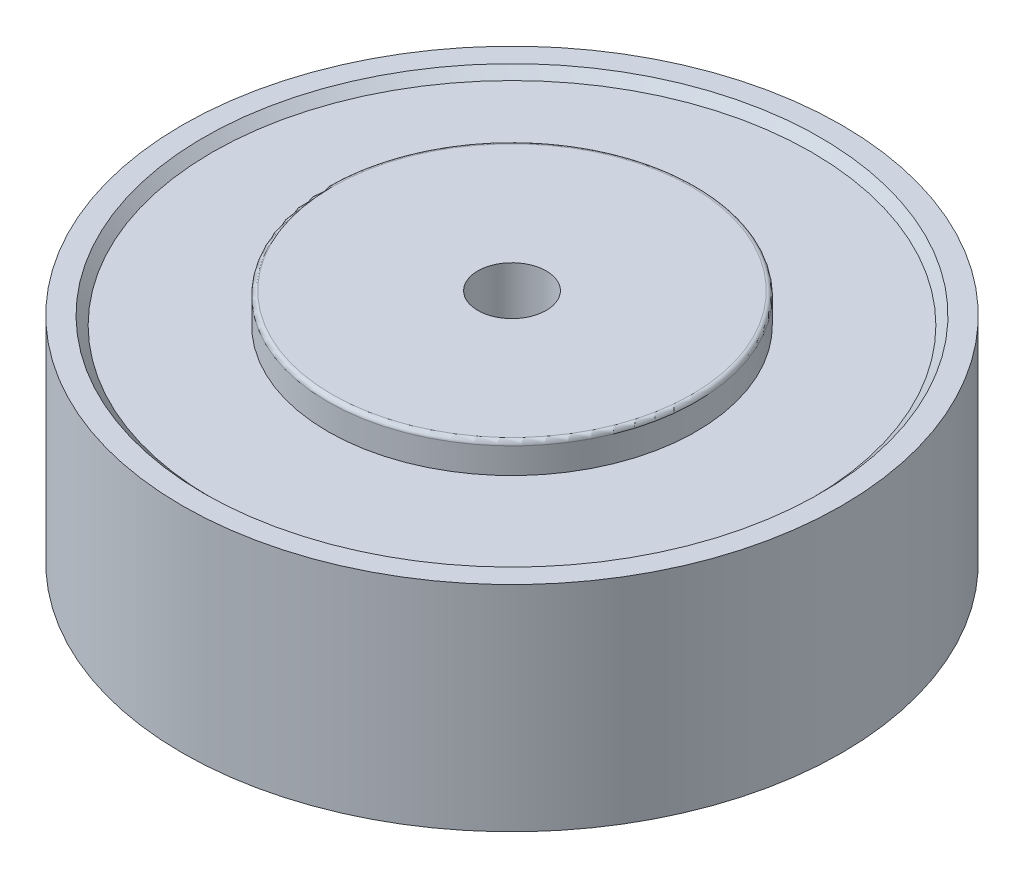
SolidWorks part; units mm, degrees
material "AISI 321 軟ｽﾃﾝﾚｽ鋼 (SS)"
ref_plane "正面" through (0, 0, 0) normal (0, 0, 1) x (1, 0, 0)
ref_plane "平面" through (0, 0, 0) normal (0, 1, 0) x (1, 0, 0)
ref_plane "右側面" through (0, 0, 0) normal (1, 0, 0) x (0, 0, -1)
sketch "ｽｹｯﾁ1" plane through (0, 0, 0) normal (0, 1, 0) x (1, 0, 0)
  arc A0 (2.7221, 38.4036) -> (35.9809, 13.6975) centre (0, 0) ccw
  arc A1 (1.3963, 35.9729) -> (34.0367, 11.7261) centre (0, 0) ccw
  circle A2 centre (0, 0) radius 38.5
extrude "ﾎﾞｽ - 押し出し1" add sketch "ｽｹｯﾁ1" along normal blind 25 contours A0 A2 region at (0, 0, 0)
sketch "ｽｹｯﾁ2" plane through (0, 25, 0) normal (0, 1, 0) x (1, 0, 0)
  arc A0 (1.3963, 35.9729) -> (34.0367, 11.7261) centre (0, 0) ccw
  circle A1 centre (0, 0) radius 36
extrude "ｶｯﾄ - 押し出し3" cut sketch "ｽｹｯﾁ2" against normal blind 1 contours A0 A1 region at (0, 25, 0)
sketch "ｽｹｯﾁ3" plane through (0, 0, 0) normal (0, -1, 0) x (1, 0, 0)
  arc A0 (1.3963, 35.9729) -> (34.0367, 11.7261) centre (0, 0) ccw
  circle A1 centre (0, 0) radius 36
extrude "ｶｯﾄ - 押し出し4" cut sketch "ｽｹｯﾁ3" against normal blind 1 contours A0 A1 region at (0, 0, 0)
chamfer "面取り1" distance 1 angle 45 2 edges at (0, 1, -36) (0, 24, 36)
sketch "ｽｹｯﾁ4" plane through (0, 1, 0) normal (0, -1, 0) x (1, 0, 0)
  arc A0 (-9.5377, 19.2687) -> (21.2022, -3.5663) centre (0, 0) ccw
  circle A1 centre (0, 0) radius 21.5
extrude "ﾎﾞｽ - 押し出し2" add sketch "ｽｹｯﾁ4" along normal blind 3.5 contours A0 A1 region at (0, 1, 0)
sketch "ｽｹｯﾁ5" plane through (0, 24, 0) normal (0, 1, 0) x (1, 0, 0)
  arc A0 (-9.5377, 19.2687) -> (21.2022, -3.5663) centre (0, 0) ccw
  circle A1 centre (0, 0) radius 21.5
extrude "ﾎﾞｽ - 押し出し3" add sketch "ｽｹｯﾁ5" along normal blind 3.5 contours A0 A1 region at (0, 24, 0)
fillet "ﾌｨﾚｯﾄ1" radius 0.5 2 edges at (0, 27.5, 21.5) (0, -2.5, -21.5)
sketch "ｽｹｯﾁ6" plane through (0, -2.5, 0) normal (0, -1, 0) x (1, 0, 0)
  circle A0 centre (0, 0) radius 4
  dimension "D1" = 8
extrude "ｶｯﾄ - 押し出し5" cut sketch "ｽｹｯﾁ6" against normal through all
